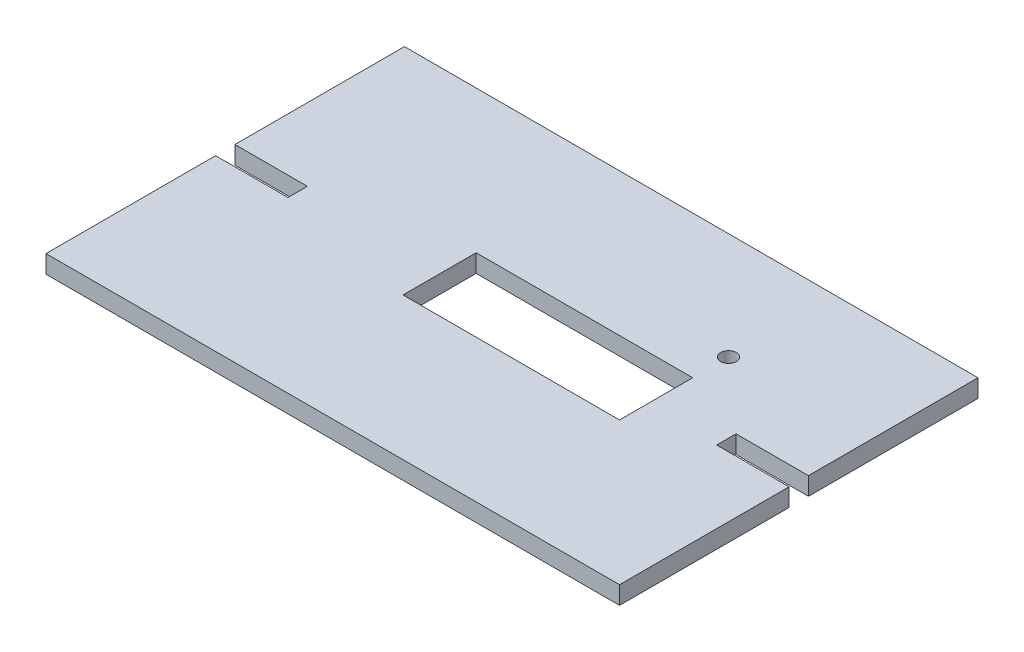
SolidWorks part; units mm, degrees
ref_plane "Front Plane" through (0, 0, 0) normal (0, 0, 1) x (1, 0, 0)
ref_plane "Top Plane" through (0, 0, 0) normal (0, 1, 0) x (1, 0, 0)
ref_plane "Right Plane" through (0, 0, 0) normal (1, 0, 0) x (0, 0, -1)
sketch "Sketch1" plane through (0, 0, 0) normal (0, 1, 0) x (1, 0, 0)
  line L0 (0, 63.5) -> (203.2, 63.5) construction
  line L1 (0, 0) -> (203.2, 0)
  line L2 (0, 0) -> (0, 60.071)
  line L3 (0, 127) -> (203.2, 127)
  line L4 (203.2, 0) -> (203.2, 60.071)
  line L5 (152.4, 76.2) -> (76.2, 76.2) construction
  line L6 (152.4, 76.2) -> (152.4, 50.8) construction
  line L7 (152.4, 50.8) -> (76.2, 50.8) construction
  line L8 (76.2, 76.2) -> (76.2, 50.8) construction
  line L9 (152.654, 76.454) -> (75.946, 76.454)
  line L10 (75.946, 76.454) -> (75.946, 50.546)
  line L11 (152.654, 50.546) -> (75.946, 50.546)
  line L12 (152.654, 76.454) -> (152.654, 50.546)
  line L13 (0, 66.929) -> (25.654, 66.929)
  line L14 (0, 66.675) -> (25.4, 66.675) construction
  line L16 (0, 60.325) -> (25.4, 60.325) construction
  line L17 (25.4, 66.675) -> (25.4, 60.325) construction
  line L18 (177.8, 66.675) -> (203.2, 66.675) construction
  line L19 (177.8, 66.675) -> (177.8, 60.325) construction
  line L20 (177.8, 60.325) -> (203.2, 60.325) construction
  line L22 (25.654, 66.929) -> (25.654, 60.071)
  line L23 (0, 60.071) -> (25.654, 60.071)
  line L24 (177.546, 66.929) -> (203.2, 66.929)
  line L25 (177.546, 66.929) -> (177.546, 60.071)
  line L26 (177.546, 60.071) -> (203.2, 60.071)
  line L27 (0, 66.929) -> (0, 127)
  line L28 (203.2, 66.929) -> (203.2, 127)
  circle A0 centre (152.654, 89.154) radius 2.7781
  dimension "D7" = 5.5562
  dimension "D1" = 203.2
  dimension "D2" = 127
  dimension "D3" = 127
  dimension "D4" = 25.4
  dimension "D5" = 76.2
  dimension "D8" = 12.7
  dimension "D9" = 25.4
  dimension "D10" = 6.35
  dimension "D6" = 0.254
  dimension "D11" = 0.254
  dimension "D12" = 0.254
extrude "Boss-Extrude1" add sketch "Sketch1" along normal blind 6.35
